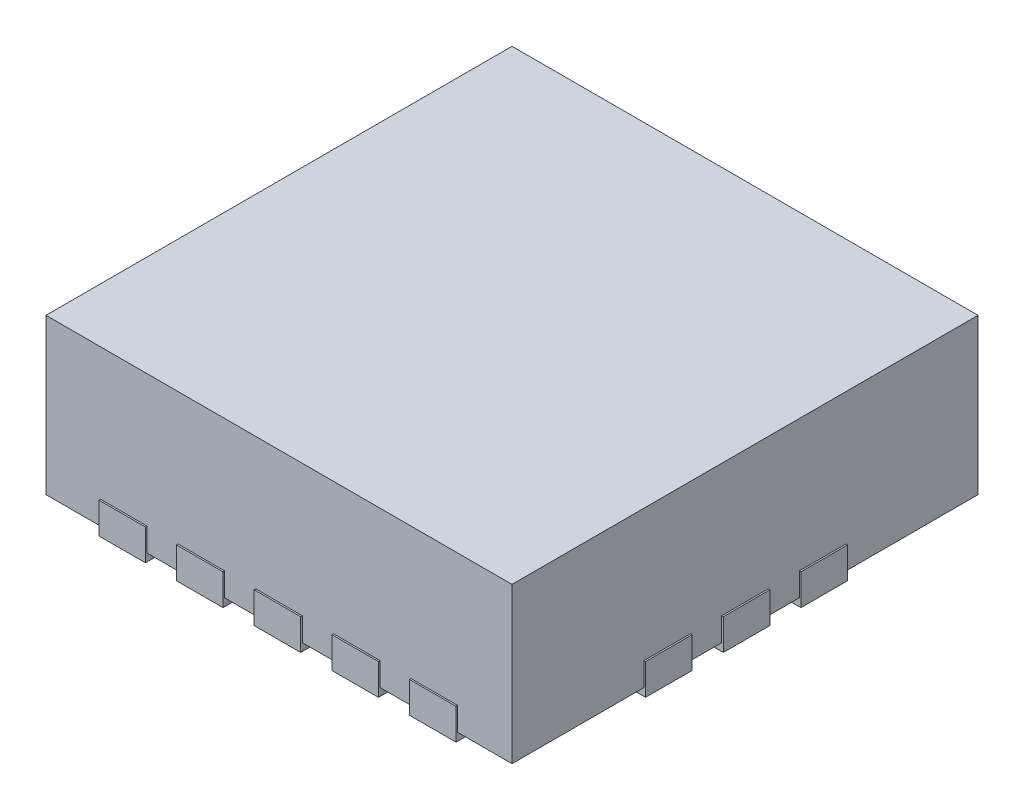
SolidWorks part; units mm, degrees
ref_plane "Front Plane" through (0, 0, 0) normal (0, 0, 1) x (1, 0, 0)
ref_plane "Top Plane" through (0, 0, 0) normal (0, 1, 0) x (1, 0, 0)
ref_plane "Right Plane" through (0, 0, 0) normal (1, 0, 0) x (0, 0, -1)
sketch "Sketch1" plane through (0, 0, 0) normal (0, 1, 0) x (1, 0, 0)
  line L1 (0, 0) -> (3, 0)
  line L2 (0, 0) -> (0, 3)
  line L3 (0, 3) -> (3, 3)
  line L4 (3, 0) -> (3, 3)
  dimension "D1" = 3
  dimension "D2" = 3
extrude "Boss-Extrude1" add sketch "Sketch1" along normal blind 1
sketch "Sketch2" plane through (0, 0, 0) normal (0, -1, 0) x (1, 0, 0)
  line L0 (2.15, 0.01) -> (2.15, -0.4)
  line L1 (1.85, 0.01) -> (2.15, 0.01)
  line L7 (1.85, 0.01) -> (1.85, -0.4)
  arc A0 (1.85, -0.4) -> (2.15, -0.4) centre (2, -0.3375) ccw
extrude "Boss-Extrude2" add sketch "Sketch2" against normal blind 0.2 from offset 0.05 separate body
pattern_linear "LPattern1" count 2 spacing 0.5 along (1, 0, 0) count 4 spacing 0.5 along (-1, 0, 0) of "Boss-Extrude2"
ref_plane "Plane1" through (0, 0, -1.5) normal (0, 0, 1) x (1, 0, 0)
sketch "Sketch5" plane through (0, 0, 0) normal (0, -1, 0) x (1, 0, 0)
  line L2 (-0.01, -0.85) -> (0.4, -0.85)
  line L3 (-0.01, -1.15) -> (-0.01, -0.85)
  line L4 (-0.01, -1.15) -> (0.4, -1.15)
  arc A0 (0.4, -1.15) -> (0.4, -0.85) centre (0.3375, -1) ccw
extrude "Boss-Extrude4" add sketch "Sketch5" against normal blind 0.2 from offset 0.05 separate body
pattern_linear "LPattern3" count 2 spacing 0.5 along (0, 0, -1) count 2 spacing 0.5 along (0, 0, -1) of "Boss-Extrude4"
ref_plane "Plane2" through (1.5, 0, 0) normal (1, 0, 0) x (0, 0, -1)
mirror "Mirror7" about plane through (1.5, 0, 0) normal (1, 0, 0) of "LPattern3", "Boss-Extrude4"
mirror "Mirror8" about plane through (0, 0, -1.5) normal (0, 0, 1) of "LPattern1", "Boss-Extrude2"
